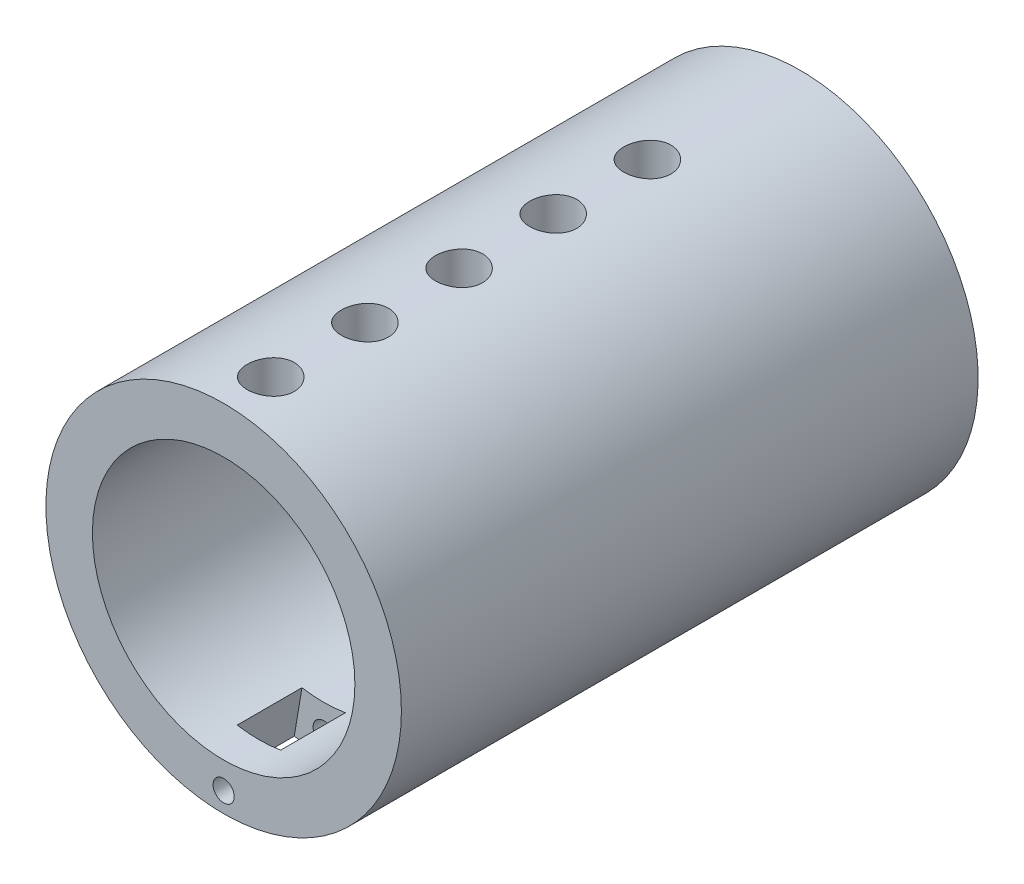
SolidWorks part; units mm, degrees
note: The reader was unsure of these and kept them because the rebuilt part matched: shared geometry of "Sketch8<3>".
ref_plane "Front Plane" through (0, 0, 0) normal (0, 0, 1) x (1, 0, 0)
ref_plane "Top Plane" through (0, 0, 0) normal (0, 1, 0) x (1, 0, 0)
ref_plane "Right Plane" through (0, 0, 0) normal (1, 0, 0) x (0, 0, -1)
sketch "Sketch1" plane through (0, 0, 0) normal (0, 0, 1) x (1, 0, 0)
  line L0 (0, 0) -> (0, 15.1022) construction
  line L1 (0, 0) -> (-2, 10.9692) construction
  line L2 (-2, 0) -> (2, 0)
  line L3 (-2, 0) -> (-2, 14.9692)
  line L4 (-2, 14.9692) -> (2, 14.9692)
  line L5 (2, 0) -> (2, 14.9692)
  line L6 (-2, 0) -> (2, 14.9692) construction
  line L7 (-2, 14.9692) -> (2, 0) construction
  line L8 (-1.5, 0) -> (-1.5, 15.0275)
  line L9 (1.5, 0) -> (1.5, 15.0275)
  circle A0 centre (0, 0) radius 11.15
  circle A1 centre (0, 0) radius 15.1022
  point P4 (0, 7.4846)
  dimension "D1" = 22.3
  dimension "D4" = 30.2044
  dimension "D2" = 4
  dimension "D3" = 4
  dimension "D5" = 0.5
  dimension "D6" = 0.5
extrude "Boss-Extrude1" add sketch "Sketch1" along normal blind 49 contours L3 A0 L5 L2 | L9 A0 L8 L2 | L5 A0 L9 L2 | L8 A0 L3 L2 | A1
sketch "Sketch4" plane through (0, 0, 49) normal (0, 0, 1) x (1, 0, 0)
  circle A0 centre (0, 0) radius 15.1022
  circle A1 centre (0, 0) radius 11.15
  dimension "D1" = 30.2044
  dimension "D2" = 22.3
sketch "Sketch2" plane through (0, 0, 0) normal (0, 0, -1) x (-1, 0, 0)
  line L0 (0, 0) -> (0, -15.1022) construction
  line L3 (-2, -14.9692) -> (2, -14.9692)
  line L5 (-2, -14.9692) -> (2, -14.9692)
  line L6 (-2, -14.9692) -> (-2, -12.9692)
  line L7 (-2, -12.9692) -> (2, -12.9692)
  line L8 (2, -14.9692) -> (2, -12.9692)
  circle A1 centre (0, 0) radius 15.1022 construction
  dimension "D1" = 2
  dimension "D2" = 2
  dimension "D3" = 2
extrude "Cut-Extrude1" cut sketch "Sketch2" against normal blind 2
sketch "Sketch6" plane through (0, 0, 0) normal (0, 0, -1) x (-1, 0, 0)
  line L0 (0, 0) -> (-1.7442, -11.0127)
  line L1 (0, 0) -> (0, -12.9692) construction
  line L2 (0, -12.9692) -> (0, -15.1022) construction
  line L3 (-1.7442, -11.0127) -> (-1.932, -12.198)
  line L4 (0, 0) -> (1.7442, -11.0127)
  line L5 (1.7442, -11.0127) -> (1.932, -12.198)
  line L6 (-1, -6.3138) -> (1, -6.3138)
  line L7 (-2, -12.9692) -> (2, -12.9692) construction
  circle A0 centre (0, 0) radius 12.35
  circle A1 centre (0, 0) radius 11.15
  circle A2 centre (0, 0) radius 11.15 construction
  circle A3 centre (0, 0) radius 15.1022 construction
  point P11 (0, -6.3138)
  circle M8 centre (0, 0) radius 11.15
  dimension "D6" = 24.7
  dimension "D1" = 12.9692
  dimension "D2" = 15.1022
  dimension "D3" = 1.2
  dimension "D4" = 2
  dimension "D5" = 18
extrude "Cut-Extrude2" cut sketch "Sketch6" against normal blind 1.1 contours L5 A0 L3 M8
sketch "Sketch7" plane through (0, 0, 0) normal (0, 1, 0) x (1, 0, 0)
  line L0 (0, 0) -> (0, -49) construction
  line L1 (-15.1022, -49) -> (15.1022, -49) construction
  line L2 (0, -47) -> (0, -49) construction
  circle A0 centre (0, -13) radius 2
  circle A1 centre (0, -21) radius 2
  circle A2 centre (0, -29) radius 2
  circle A3 centre (0, -37) radius 2
  circle A4 centre (0, -45) radius 2
  dimension "D1" = 4
  dimension "D2" = 4
  dimension "D3" = 4
  dimension "D4" = 4
  dimension "D5" = 4
  dimension "D9" = 8
  dimension "D6" = 13
  dimension "D7" = 8
  dimension "D8" = 8
  dimension "D10" = 8
  dimension "D11" = 2
extrude "Pin hole" cut sketch "Sketch7" along normal through all
sketch "Sketch8" plane through (0, 0, 49) normal (0, 0, 1) x (1, 0, 0)
  line L0 (0, 0) -> (-2.5, -14.8938)
  line L1 (0, 0) -> (2.5, -14.8938)
  line L2 (0, 0) -> (0, -15.1022) construction
  line L3 (-1.0071, -6) -> (1.0071, -6)
  circle A0 centre (0, 0) radius 15.1022
  circle A1 centre (0, 0) radius 15.1022 construction
  arc A2 (-1.8458, -10.9962) -> (1.8458, -10.9962) centre (0, 0) ccw
  circle A3 centre (0, 0) radius 11.15 construction
  circle A4 centre (0, -13.4022) radius 0.9
  point P15 (0, -6)
  circle M2 centre (0, 0) radius 15.1022
  circle M3 centre (0, 0) radius 11.15
  dimension "D3" = 1.8
  dimension "D1" = 6
  dimension "D2" = 5
  dimension "D4" = 1.7
extrude "Cut-Extrude4" cut sketch "Sketch8" against normal blind 5.5 from offset 3 contours L2 A4 A0 L1 M3 | L2 A2 L0 A4 M2 offset against normal yes
extrude "Cut-Extrude5" cut sketch "Sketch8<3>" against normal blind 15 contours A4 L2 | L2 A4
sketch "Sketch8<3>" plane through (0, 0, 49) normal (0, 0, 1) x (1, 0, 0) same geometry as "Sketch8"
sketch "Sketch9" plane through (0, 0, 0) normal (0, 0, -1) x (-1, 0, 0)
  line L0 (2, 15.1022) -> (2, 14.9692)
  line L1 (0, 15.1022) -> (2, 15.1022)
  line L2 (0, 15.1022) -> (0, 11.15)
  line L3 (0, 11.15) -> (2, 11.15)
  line L4 (2, 15.1022) -> (2, 11.15)
  line L5 (2, 14.9692) -> (2, 11.15)
  line L6 (2, 11.15) -> (2, 10.9692)
  arc A0 (2, -14.9692) -> (-2, -14.9692) centre (0, 0) ccw construction
  arc A1 (1.7442, -11.0127) -> (-1.7442, -11.0127) centre (0, 0) ccw construction
  dimension "D1" = 2
  dimension "D2" = 4
  dimension "D3" = 3.8192
equation "\"ET_circle_d\"= 0.3mm'add to diameter of outer circle"
